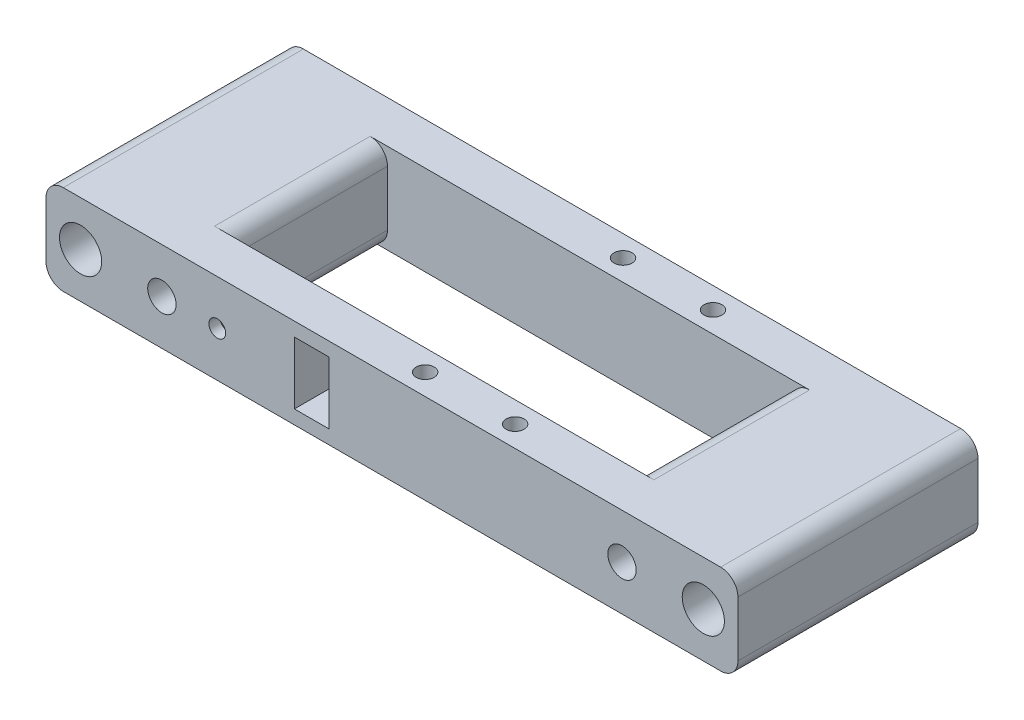
SolidWorks part; units mm, degrees
ref_plane "Front Plane" through (0, 0, 0) normal (0, 0, 1) x (1, 0, 0)
ref_plane "Top Plane" through (0, 0, 0) normal (0, 1, 0) x (1, 0, 0)
ref_plane "Right Plane" through (0, 0, 0) normal (1, 0, 0) x (0, 0, -1)
sketch "Sketch1" plane through (0, 0, 0) normal (0, 0, 1) x (1, 0, 0)
  line L0 (-58.5, 26) -> (-58.5, 0) construction
  line L1 (0, 0) -> (-100, 0)
  line L2 (0, 0) -> (0, 26)
  line L3 (0, 26) -> (-100, 26)
  line L4 (-100, 0) -> (-100, 26)
  circle A0 centre (-90, 13) radius 6.1
  circle A1 centre (-66.5, 13) radius 4.1
  point P9 (-100, 13)
  dimension "D3" = 12.2
  dimension "D4" = 8.2
  dimension "D1" = 100
  dimension "D2" = 26
  dimension "D5" = 23.5
  dimension "D6" = 10
  dimension "D7" = 8
  dimension "D8" = 41.5
extrude "Boss-Extrude1" add sketch "Sketch1" along normal blind 40
sketch "Sketch2" plane through (0, 0, 0) normal (0, 0, -1) x (-1, 0, 0)
  line L1 (100, 26) -> (0, 26)
  line L2 (100, 26) -> (100, 0)
  line L3 (100, 0) -> (0, 0)
  line L4 (0, 26) -> (0, 0)
extrude "Boss-Extrude2" add sketch "Sketch2" along normal blind 29.4
sketch "Sketch3" plane through (0, 26, 0) normal (0, 1, 0) x (1, 0, 0)
  line L0 (0, -40) -> (0, 29.4) construction
  line L1 (0, 17.2) -> (-58.5, 17.2)
  line L2 (0, 17.2) -> (0, -27.8)
  line L3 (0, -27.8) -> (-58.5, -27.8)
  line L4 (-58.5, 17.2) -> (-58.5, -27.8)
  line L5 (-100, -40) -> (-100, 29.4) construction
  line L6 (-100, 29.4) -> (0, 29.4) construction
  line L7 (0, -40) -> (-100, -40) construction
  dimension "D1" = 41.5
  dimension "D2" = 12.2
  dimension "D3" = 12.2
extrude "Cut-Extrude1" cut sketch "Sketch3" against normal up to next
mirror "Mirror2" about plane through (0, 0, 40) normal (-1, 0, 0) of "Boss-Extrude2", "Cut-Extrude1", "Boss-Extrude1"
sketch "Sketch4" plane through (0, 26, 0) normal (0, 1, 0) x (1, 0, 0)
  line L0 (-100, 29.4) -> (100, 29.4) construction
  line L1 (-5.5, 29.4) -> (-5.5, 17.2) construction
  line L2 (58.5, 17.2) -> (-58.5, 17.2) construction
  line L3 (58.5, 17.2) -> (58.5, -27.8) construction
  circle A0 centre (3.5, 23.3) radius 2.6
  circle A1 centre (29.5, 23.3) radius 2.6
  dimension "D1" = 6.1
  dimension "D3" = 9
  dimension "D4" = 26
  dimension "D5" = 5.2
  dimension "D2" = 64
extrude "Cut-Extrude2" cut sketch "Sketch4" against normal through all
sketch "Sketch5" plane through (0, 0, 0) normal (0, -1, 0) x (1, 0, 0)
  line L1 (34.2343, -23.3) -> (31.8671, -19.2)
  line L2 (31.8671, -19.2) -> (27.1329, -19.2)
  line L3 (27.1329, -19.2) -> (24.7657, -23.3)
  line L4 (24.7657, -23.3) -> (27.1329, -27.4)
  line L5 (27.1329, -27.4) -> (31.8671, -27.4)
  line L6 (31.8671, -27.4) -> (34.2343, -23.3)
  line L7 (-1.2343, -23.3) -> (1.1329, -27.4)
  line L8 (1.1329, -27.4) -> (5.8671, -27.4)
  line L9 (5.8671, -27.4) -> (8.2343, -23.3)
  line L10 (8.2343, -23.3) -> (5.8671, -19.2)
  line L11 (5.8671, -19.2) -> (1.1329, -19.2)
  line L12 (1.1329, -19.2) -> (-1.2343, -23.3)
  circle A0 centre (29.5, -23.3) radius 4.1 construction
  circle A1 centre (3.5, -23.3) radius 4.1 construction
  dimension "D1" = 8.2
  dimension "D2" = 8.2
extrude "Cut-Extrude3" cut sketch "Sketch5" against normal blind 4
ref_plane "Plane1" through (0, 0, 5.3) normal (0, 0, 1) x (1, 0, 0)
mirror "Mirror3" about plane through (0, 0, 5.3) normal (0, 0, 1) of "Cut-Extrude3", "Cut-Extrude2"
sketch "Sketch6" plane through (0, 0, 40) normal (0, 0, 1) x (1, 0, 0)
  line L0 (-8.1, 26) -> (-8.1, 0) construction
  line L1 (100, 26) -> (-100, 26) construction
  line L2 (-100, 0) -> (100, 0) construction
  line L3 (0.9, 26) -> (0.9, 4) construction
  line L4 (-100, 26) -> (-100, 0) construction
  line L5 (-18.2, 22) -> (-28.2, 22)
  line L6 (-18.2, 22) -> (-18.2, 4)
  line L7 (-18.2, 4) -> (-28.2, 4)
  line L8 (-28.2, 22) -> (-28.2, 4)
  point P12 (-28.2, 13)
  point P15 (-100, 13)
  dimension "D1" = 9
  dimension "D2" = 10.1
  dimension "D3" = 10
  dimension "D4" = 18
extrude "Cut-Extrude4" cut sketch "Sketch6" against normal up to vertex (14 mm away) up to point (0, -58.5, 26)
fillet "Fillet1" radius 5 8 edges at (58.5, 0, 5.3) (-58.5, 0, 5.3) (58.5, 26, 5.3) (100, 0, 5.3) (100, 26, 5.3) (-100, 0, 5.3) (-100, 26, 5.3) (-58.5, 26, 5.3)
sketch "Sketch7" plane through (0, 0, 27.8) normal (0, 0, -1) x (-1, 0, 0)
  line L0 (58.5, 5) -> (58.5, 21) construction
  circle A0 centre (50.5, 13) radius 5
  point P4 (58.5, 13)
  dimension "D1" = 10
  dimension "D2" = 8
extrude "Cut-Extrude5" cut sketch "Sketch7" against normal blind 9 contours A0
sketch "Sketch8" plane through (0, 0, 36.8) normal (0, 0, -1) x (-1, 0, 0)
  circle A0 centre (50.5, 13) radius 2.4278
extrude "Cut-Extrude6" cut sketch "Sketch8" against normal up to next
